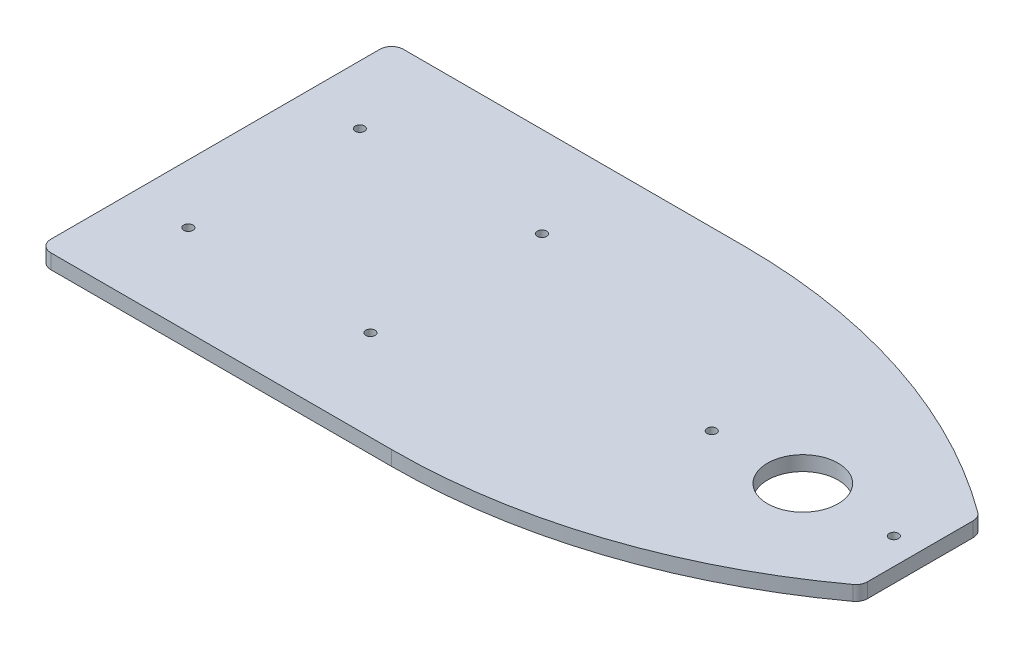
SolidWorks part; units mm, degrees
material "PLA"
ref_plane "Front" through (0, 0, 0) normal (0, 0, 1) x (1, 0, 0)
ref_plane "Top" through (0, 0, 0) normal (0, 1, 0) x (1, 0, 0)
ref_plane "Right" through (0, 0, 0) normal (1, 0, 0) x (0, 0, -1)
sketch "Sketch1" plane through (0, 0, 0) normal (0, 1, 0) x (1, 0, 0)
  line L1 (76.2, -38.1) -> (-76.2, -38.1)
  line L2 (76.2, -38.1) -> (76.2, 38.1)
  line L3 (76.2, 38.1) -> (-76.2, 38.1)
  line L4 (-76.2, -38.1) -> (-76.2, 38.1)
  line L5 (76.2, -38.1) -> (-76.2, 38.1) construction
  line L6 (76.2, 38.1) -> (-76.2, -38.1) construction
  point P0 (0, 0)
  dimension "D1" = 76.2
  dimension "D2" = 152.4
extrude "Boss-Extrude1" add sketch "Sketch1" along normal blind 3.175
sketch "Sketch4" plane through (0, 3.175, 0) normal (0, 1, 0) x (1, 0, 0)
  line L0 (0, 38.1) -> (76.2, 38.1)
  line L1 (76.2, 38.1) -> (-76.2, 38.1) construction
  line L2 (76.2, 38.1) -> (76.2, 12.7)
  line L3 (76.2, -38.1) -> (76.2, 38.1) construction
  line L4 (76.2, -38.1) -> (76.2, -12.7)
  line L5 (76.2, -38.1) -> (0, -38.1)
  line L6 (-76.2, -38.1) -> (76.2, -38.1) construction
  arc A0 (0, -38.1) -> (76.2, -12.7) centre (0, 88.9) ccw
  arc A1 (0, 38.1) -> (76.2, 12.7) centre (0, -88.9) cw
  dimension "D3" = 127
  dimension "D4" = 127
  dimension "D1" = 25.4
  dimension "D2" = 25.4
extrude "Cut-Extrude1" cut sketch "Sketch4" against normal blind 3.175
fillet "Fillet2" radius 2.54 2 edges at (76.2, 1.5875, 12.7) (76.2, 1.5875, -12.7)
fillet "Fillet3" radius 2.54 2 edges at (-76.2, 1.5875, 38.1) (-76.2, 1.5875, -38.1)
sketch "Sketch5" plane through (0, 3.175, 0) normal (0, 1, 0) x (1, 0, 0)
  line L0 (-55, 0) -> (55, 0) construction
  line L1 (76.2, -11.422) -> (76.2, 11.422) construction
  circle A0 centre (50.8, 0) radius 7.62
  dimension "D1" = 15.24
  dimension "D2" = 25.4
extrude "Cut-Extrude2" cut sketch "Sketch5" against normal blind 3.175
sketch "Sketch6" plane through (0, 3.175, 0) normal (0, 1, 0) x (1, 0, 0)
  line L1 (-63.5, 18.542) -> (-63.5, 0)
  line L4 (-24.13, 18.542) -> (-24.13, -18.542)
  line L5 (-1.7463, 0) -> (1.7463, 0) construction
  line L6 (-63.5, 0) -> (-63.5, -18.542)
  circle A5 centre (-63.5, 18.542) radius 1.0033
  circle A6 centre (-24.13, 18.542) radius 1.0033
  circle A7 centre (-24.13, -18.542) radius 1.0033
  circle A8 centre (-63.5, -18.542) radius 1.0033
  point P9 (0, 0)
  dimension "D1" = 18.542
  dimension "D2" = 2.0066
  dimension "D4" = 2.0066
  dimension "D5" = 2.0066
  dimension "D6" = 2.0066
  dimension "D3" = 18.542
sketch "Sketch7" plane through (0, 3.175, 0) normal (0, 1, 0) x (1, 0, 0)
  line L0 (50.8, -7.62) -> (50.8, 7.62)
  line L1 (50.8, 0) -> (70.485, 0)
  line L2 (-1.7463, 0) -> (1.7463, 0) construction
  line L3 (50.8, 0) -> (31.115, 0)
  circle A0 centre (50.8, 0) radius 7.62 construction
  circle A1 centre (70.485, 0) radius 1.0033
  circle A2 centre (31.115, 0) radius 1.0033
  dimension "D3" = 2.0066
  dimension "D4" = 2.0066
  dimension "D1" = 19.685
  dimension "D2" = 19.685
extrude "Cut-Extrude4" cut sketch "Sketch7" against normal through all contours A2 | A1 region at (30.1401, 3.175, 0)
extrude "Cut-Extrude5" cut sketch "Sketch6" against normal through all contours A5 | A6 | A7 | A8 region at (-62.8106, 3.175, 17.8526) region at (-64.1894, 3.175, -19.2314) region at (-23.4406, 3.175, 17.8526) region at (-24.8194, 3.175, -19.2314)
